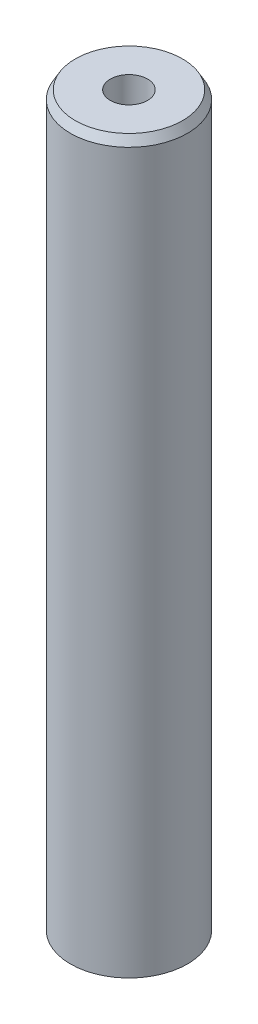
SolidWorks part; units mm, degrees
ref_plane "Front Plane" through (0, 0, 0) normal (0, 0, 1) x (1, 0, 0)
ref_plane "Top Plane" through (0, 0, 0) normal (0, 1, 0) x (1, 0, 0)
ref_plane "Right Plane" through (0, 0, 0) normal (1, 0, 0) x (0, 0, -1)
sketch "Sketch1" plane through (0, 0, 0) normal (0, 1, 0) x (1, 0, 0)
  circle A0 centre (0, 0) radius 30
  dimension "SHAFT_OD" = 60
extrude "Boss-Extrude1" add sketch "Sketch1" along normal blind 375.8215
sketch "Sketch2" plane through (0, 0, 0) normal (0, 1, 0) x (1, 0, 0)
  circle A0 centre (0, 0) radius 9.5393
  dimension "BORE_D" = 19.0786
extrude "Cut-Extrude1" cut sketch "Sketch2" along normal through all
chamfer "Chamfer1" distance 4.3728 angle 30 2 edges at (0, 375.8215, 30) (0, 0, 30) first distance on face at (0, 375.8215, 30) first distance on face at (0, 0, 9.5393)
